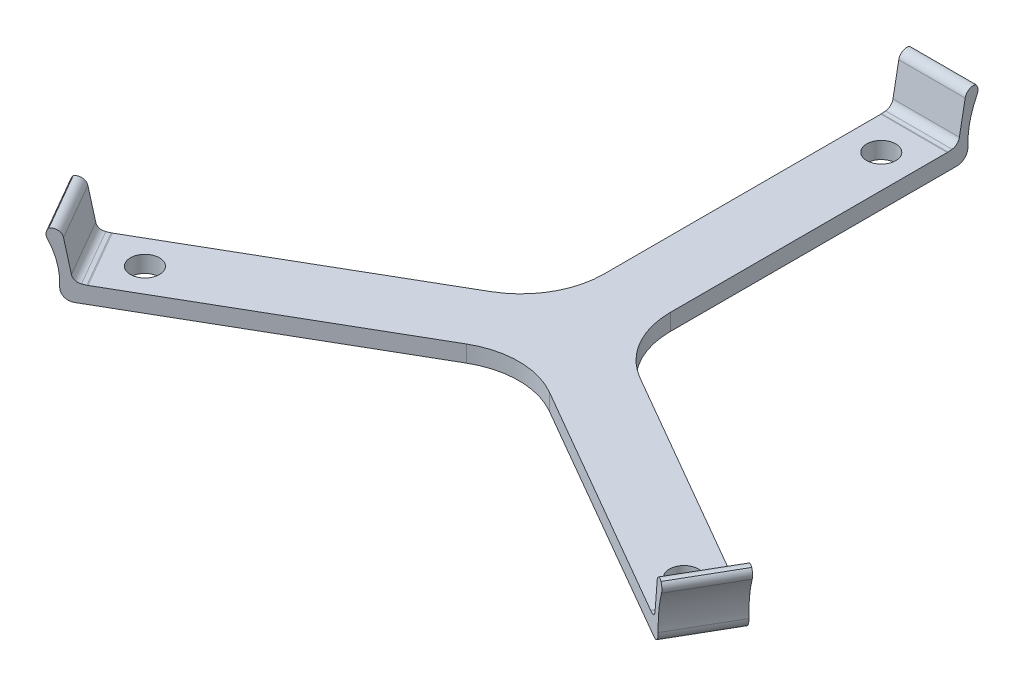
SolidWorks part; units mm, degrees
ref_plane "Front Plane" through (0, 0, 0) normal (0, 0, 1) x (1, 0, 0)
ref_plane "Top Plane" through (0, 0, 0) normal (0, 1, 0) x (1, 0, 0)
ref_plane "Right Plane" through (0, 0, 0) normal (1, 0, 0) x (0, 0, -1)
sketch "Sketch1" plane through (0, 0, 0) normal (0, 1, 0) x (1, 0, 0)
  line L1 (0, 0) -> (8, 0)
  line L2 (0, 0) -> (0, 41.5)
  line L3 (0, 41.5) -> (8, 41.5)
  line L4 (8, 0) -> (8, 41.5)
  circle A0 centre (4, 37.5) radius 1.75
  point P7 (0, 0)
  point P9 (6.5835, 45.2323)
  dimension "D3" = 4
  dimension "D1" = 41.5
  dimension "D2" = 8
  dimension "D4" = 4
ref_plane "Plane1" through (4, 0, 0) normal (1, 0, 0) x (0, 0, -1)
sketch "Sketch2" plane through (4, 0, 0) normal (1, 0, 0) x (0, 0, -1)
extrude "Boss-Extrude2" add sketch "Sketch1" along normal blind 2
sketch "Sketch3" plane through (4, 0, 0) normal (1, 0, 0) x (0, 0, -1)
  line L0 (0, 0) -> (0, 17.8781) construction
pattern_circular "CirPattern1" count 3 over 360 about axis through (4, 0, 0) along (0, 1, 0) of "Boss-Extrude2" reverse direction yes
sketch "Sketch8" plane through (4, 0, 0) normal (1, 0, 0) x (0, 0, -1)
  line L0 (41.5, 0) -> (42.6211, 0)
  line L1 (45.5, 7.0135) -> (43.8859, 8.0607)
  line L2 (43.8859, 8.0607) -> (42.7717, 2.127)
  line L3 (42.7717, 2.127) -> (41.5, 2)
  line L4 (41.5, 2) -> (41.5, 0)
  line L6 (41.5, 2) -> (41.5, 0) construction
  arc A0 (42.6211, 0) -> (43.9451, 1.3744) centre (42.6211, 1.3249) ccw
  arc A1 (43.9451, 1.3744) -> (45.5, 7.0135) centre (53.6339, 1.7368) cw
  point P7 (48.1768, 7.7075)
  point P11 (46.539, 7.6132)
  point P12 (45.4804, 1.1816)
  point P13 (47.6832, 7.217)
  point P14 (46.4605, 8.0505)
  point P17 (0, 0)
  point P18 (41.5, 0)
  dimension "D1" = 2
  dimension "D2" = 0
  dimension "D3" = 4
extrude "Boss-Extrude4" add sketch "Sketch8" along normal blind 4 and the other way blind 4
fillet "Fillet4" radius 1 2 edges at (4, 8.0607, -43.8859) (4, 7.0135, -45.5)
fillet "Fillet5" radius 1 2 edges at (4, 2, -41.5) (4, 2.127, -42.7717)
pattern_circular "CirPattern2" count 3 every 120 about axis through (4, 0, 0) along (0, 1, 0) of "Fillet5", "Fillet4", "Boss-Extrude4" reverse direction yes
fillet "Fillet6" radius 10 3 edges at (8, 1, -2.3094) (4, 1, 4.6188) (0, 1, -2.3094)
